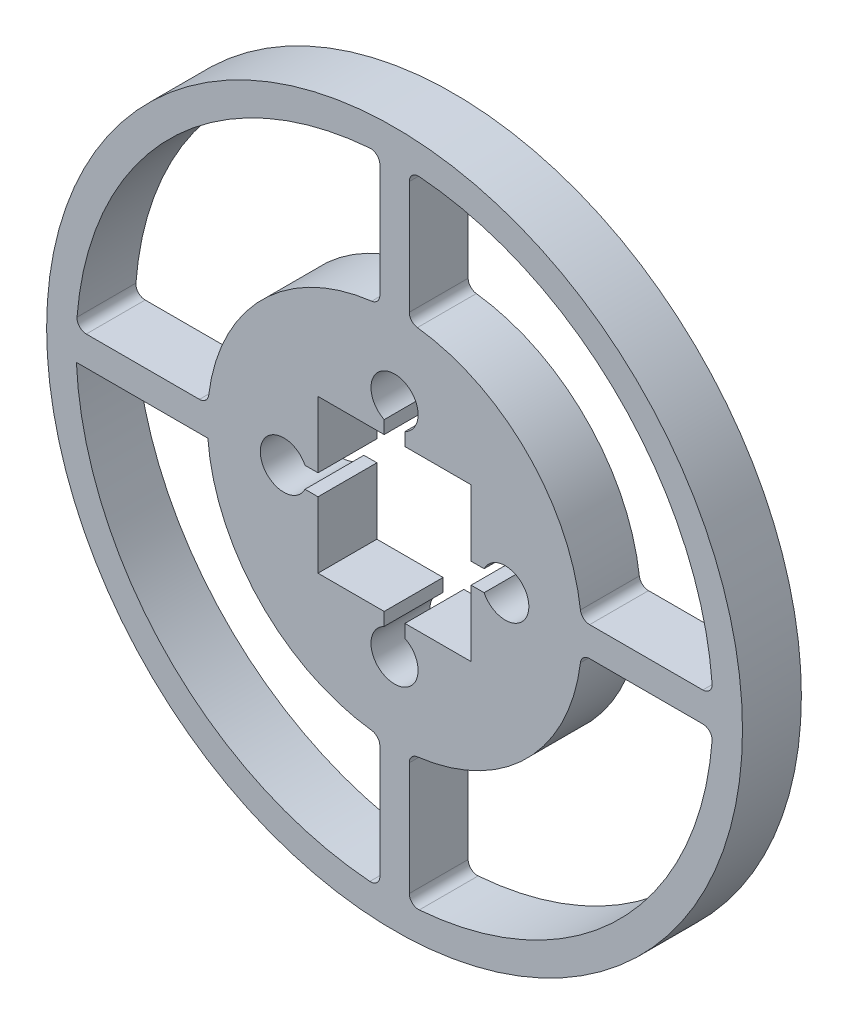
SolidWorks part; units mm, degrees
material "AISI 1020"
ref_plane "Front Plane" through (0, 0, 0) normal (0, 0, 1) x (1, 0, 0)
ref_plane "Top Plane" through (0, 0, 0) normal (0, 1, 0) x (1, 0, 0)
ref_plane "Right Plane" through (0, 0, 0) normal (1, 0, 0) x (0, 0, -1)
other "Center of Mass"
sketch "Sketch1" plane through (0, 0, 0) normal (0, 0, 1) x (1, 0, 0)
  line L0 (-11.938, 0) -> (0, 0) construction
  line L1 (-8.255, 8.255) -> (8.255, 8.255)
  line L2 (-8.255, 8.255) -> (-8.255, -8.255)
  line L3 (-8.255, -8.255) -> (8.255, -8.255)
  line L4 (8.255, 8.255) -> (8.255, -8.255)
  line L5 (0, 0) -> (0, 11.938) construction
  line L6 (11.938, 0) -> (0, 0) construction
  line L7 (0, 0) -> (0, -11.938) construction
  line L9 (-9.6571, 1.1176) -> (9.6571, 1.1176)
  line L10 (-9.6571, 1.1176) -> (-9.6571, -1.1176)
  line L11 (-9.6571, -1.1176) -> (9.6571, -1.1176)
  line L12 (9.6571, 1.1176) -> (9.6571, -1.1176)
  line L13 (-1.1176, 9.6571) -> (1.1176, 9.6571)
  line L14 (-1.1176, 9.6571) -> (-1.1176, -9.6571)
  line L15 (-1.1176, -9.6571) -> (1.1176, -9.6571)
  line L16 (1.1176, 9.6571) -> (1.1176, -9.6571)
  line L17 (-1.5875, 20.1305) -> (-1.5875, 34.3041)
  line L19 (1.5875, 20.1305) -> (1.5875, 34.3041)
  line L20 (20.1305, 1.5875) -> (34.3041, 1.5875)
  line L21 (20.1305, -1.5875) -> (34.3041, -1.5875)
  line L22 (1.5875, -20.1305) -> (1.5875, -34.3041)
  line L23 (-1.5875, -20.1305) -> (-1.5875, -34.3041)
  line L24 (-20.1305, -1.5875) -> (-34.3041, -1.5875)
  line L25 (-20.1305, 1.5875) -> (-34.3041, 1.5875)
  circle A1 centre (0, 11.938) radius 2.54
  circle A2 centre (0, -11.938) radius 2.54
  circle A3 centre (11.938, 0) radius 2.54
  circle A4 centre (-11.938, 0) radius 2.54
  circle A68 centre (0, 0) radius 37.5158
  arc A73 (-1.5875, 34.3041) -> (-34.3041, 1.5875) centre (0, 0) ccw
  arc A75 (-1.5875, 20.1305) -> (-20.1305, 1.5875) centre (0, 0) ccw
  arc A76 (20.1305, 1.5875) -> (1.5875, 20.1305) centre (0, 0) ccw
  arc A77 (34.3041, 1.5875) -> (1.5875, 34.3041) centre (0, 0) ccw
  arc A78 (1.5875, -20.1305) -> (20.1305, -1.5875) centre (0, 0) ccw
  arc A79 (1.5875, -34.3041) -> (34.3041, -1.5875) centre (0, 0) ccw
  arc A80 (-20.1305, -1.5875) -> (-1.5875, -20.1305) centre (0, 0) ccw
  arc A81 (-34.3041, -1.5875) -> (-1.5875, -34.3041) centre (0, 0) ccw
  point P7 (8.255, 0)
  point P8 (0, 8.255)
  point P46 (0, 0)
  point P54 (0, 0)
  point P70 (0, 0)
  point P77 (0, 0)
  point P104 (0, 0)
  dimension "D2" = 2.2352
  dimension "D4" = 5.08
  dimension "D6" = 3.175
  dimension "D7" = 40.386
  dimension "D5" = 75.0316
  dimension "D1" = 16.51
  dimension "D3" = 11.938
  dimension "D8" = 3.175
extrude "Boss-Extrude1" add sketch "Sketch1" along normal blind 6.35 contours A4 L9 L2 L1 L14 A1 L16 L4 A3 L11 L3 A2 region at (-36.4547, 0, 0)
fillet "Fillet2" radius 1 14 edges at (1.5875, -34.3041, 3.175) (34.3041, -1.5875, 3.175) (20.1305, -1.5875, 3.175) (1.5875, -20.1305, 3.175) (-1.5875, -20.1305, 3.175) (-1.5875, -34.3041, 3.175) (-20.1305, 1.5875, 3.175) (-1.5875, 20.1305, 3.175) (1.5875, 34.3041, 3.175) (-1.5875, 34.3041, 3.175) (1.5875, 20.1305, 3.175) (20.1305, 1.5875, 3.175) (34.3041, 1.5875, 3.175) (-34.3041, 1.5875, 3.175)
